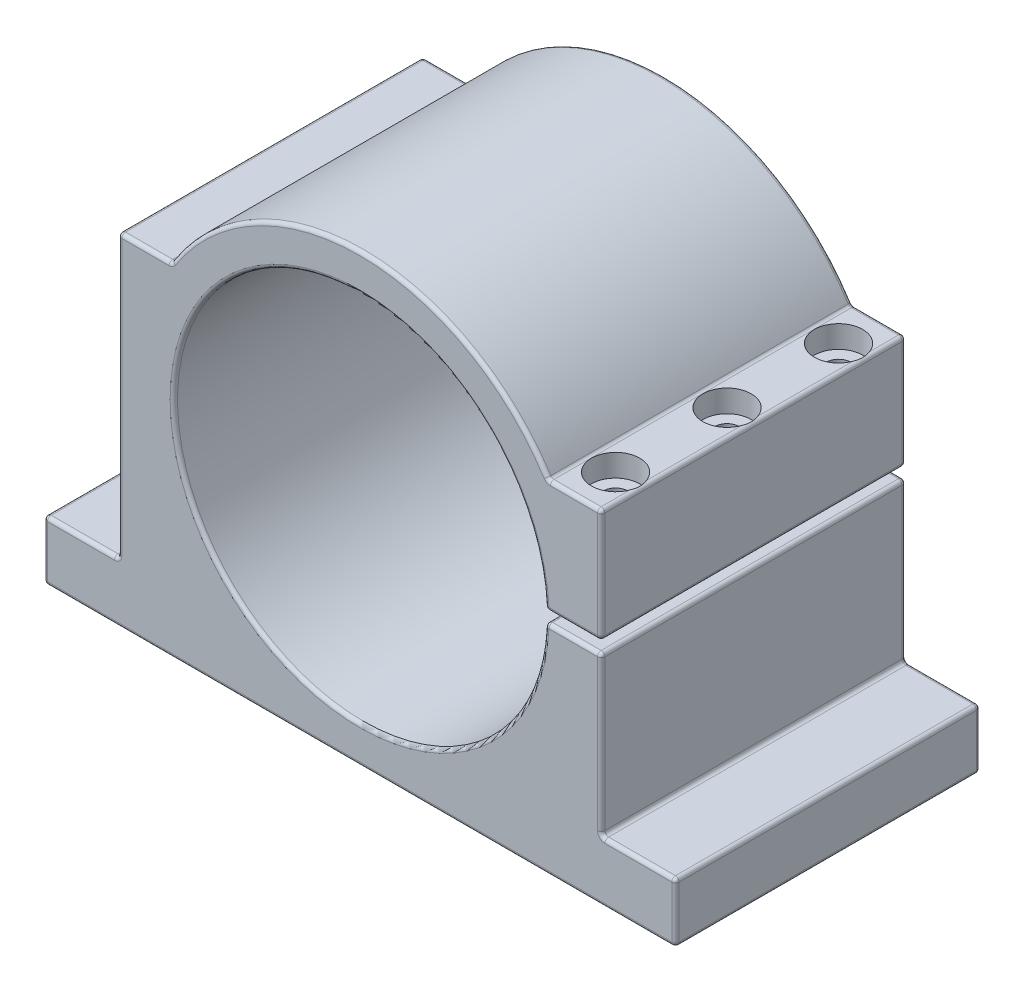
SolidWorks part; units mm, degrees
ref_plane "Спереди" through (0, 0, 0) normal (0, 0, 1) x (1, 0, 0)
ref_plane "Сверху" through (0, 0, 0) normal (0, 1, 0) x (1, 0, 0)
ref_plane "Справа" through (0, 0, 0) normal (1, 0, 0) x (0, 0, -1)
sketch "Эскиз1" plane through (0, 0, 0) normal (0, 0, 1) x (1, 0, 0)
  line L0 (0, 0) -> (0, -60) construction
  line L1 (85, -60) -> (-85, -60)
  line L2 (-85, -60) -> (-85, -44)
  line L3 (-85, -44) -> (-65, -44)
  line L4 (-65, -44) -> (-65, 32)
  line L5 (-65, 32) -> (-38.4187, 32)
  line L6 (65, 32) -> (38.4187, 32)
  line L7 (65, -44) -> (65, 32)
  line L8 (85, -44) -> (65, -44)
  line L9 (85, -60) -> (85, -44)
  line L10 (201.7453, 552.2596) -> (1355.0786, 552.2596) construction
  line L11 (0, 1.5) -> (95.6878, 1.5)
  line L12 (0, 1.5) -> (0, -1.5)
  line L13 (0, -1.5) -> (95.6878, -1.5)
  line L14 (95.6878, 1.5) -> (95.6878, -1.5)
  circle A0 centre (0, 0) radius 50
  circle A1 centre (0, 0) radius 60
  point P3 (0, -50)
  point P22 (51.7094, 32)
  dimension "D1" = 100
  dimension "D7" = 10
  dimension "D2" = 170
  dimension "D3" = 10
  dimension "D4" = 16
  dimension "D5" = 92
  dimension "D6" = 130
  dimension "D8" = 3
  dimension "D9" = 13.2906
extrude "Бобышка-Вытянуть1" add sketch "Эскиз1" along normal mid plane 82 contours A1 L1 L9 L8 L7 L13 | L5 A1 L13 A0 | A1 L5 L4 L3 L2 L1 | L6 A1 L5 A0 | A1 L11 L7 L6 | L11 A1 L6 A0
sketch "Эскиз2" plane through (0, 32, 0) normal (0, 1, 0) x (1, 0, 0)
  line L0 (57.8772, 41) -> (57.8772, -41) construction
  line L1 (65, 41) -> (50.7543, 41) construction
  line L2 (65, -41) -> (50.7543, -41) construction
  circle A0 centre (57.8772, 30) radius 6.5
  circle A1 centre (57.8772, 0) radius 6.5
  circle A2 centre (57.8772, -30) radius 6.5
  dimension "D3" = 13
  dimension "D1" = 30
  dimension "D2" = 30
extrude "Вырез-Вытянуть1" cut sketch "Эскиз2" against normal blind 6
sketch "Эскиз3" plane through (0, 32, 0) normal (0, 1, 0) x (1, 0, 0)
  circle A0 centre (57.8772, 30) radius 3.25
  circle A1 centre (57.8772, 0) radius 3.25
  circle A2 centre (57.8772, -30) radius 3.25
  dimension "D1" = 6.5
extrude "Вырез-Вытянуть2" cut sketch "Эскиз3" against normal up to surface (33.5 mm away) up to face at (57.4887, -1.5, 0)
sketch "Эскиз4" plane through (0, -1.5, 0) normal (0, 1, 0) x (1, 0, 0)
  circle A0 centre (57.8772, 30) radius 2.35
  circle A1 centre (57.8772, 0) radius 2.35
  circle A2 centre (57.8772, -30) radius 2.35
  dimension "D1" = 4.7
extrude "Вырез-Вытянуть3" cut sketch "Эскиз4" against normal blind 30
fillet "Скругление1" radius 1 42 edges at (-85, -44, 0) (-85, -60, 0) (-65, -44, 0) (-65, 32, 0) (50.7543, 32, 0) (-50.7543, 32, 0) (65, 1.5, 0) (65, 32, 0) (65, -1.5, 0) (85, -60, 0) (85, -44, 0) (65, -44, 0) (49.9775, -1.5, 0) (49.9775, 1.5, 0) (-50, 0, -41) (57.4887, 1.5, -41) (65, 16.75, -41) (57.8772, 32, -41) (0, 60, -41) (-57.8772, 32, -41) (-65, -6, -41) (-75, -44, -41) (-85, -52, -41) (0, -60, -41) (85, -52, -41) (75, -44, -41) (65, -22.75, -41) (57.4887, -1.5, -41) (65, -22.75, 41) (75, -44, 41) (85, -52, 41) (0, -60, 41) (-85, -52, 41) (-75, -44, 41) (-65, -6, 41) (-57.8772, 32, 41) (0, 60, 41) (57.8772, 32, 41) (65, 16.75, 41) (57.4887, 1.5, 41) (-50, 0, 41) (57.4887, -1.5, 41)
